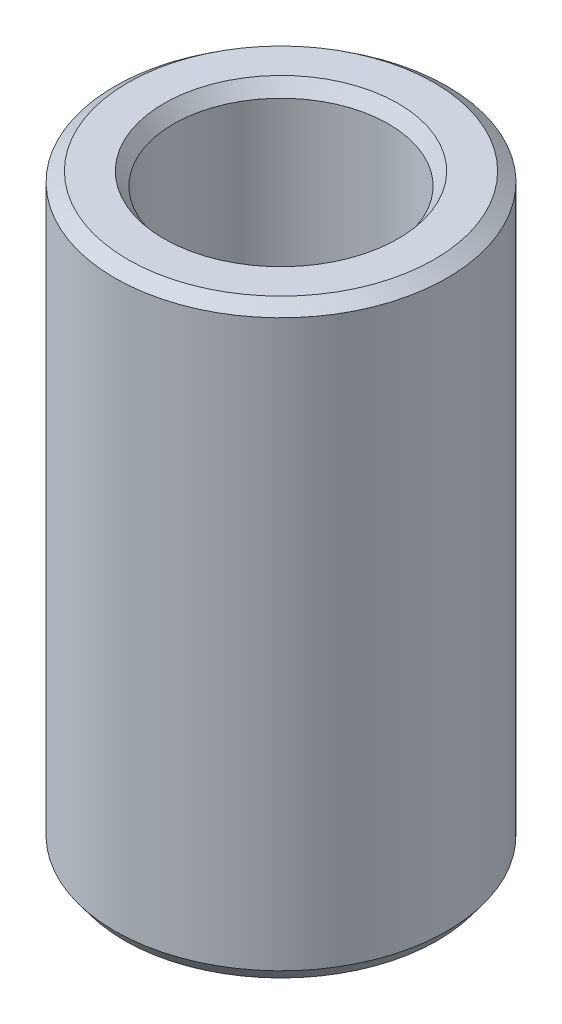
SolidWorks part; units mm, degrees
ref_plane "Front Plane" through (0, 0, 0) normal (0, 0, 1) x (1, 0, 0)
ref_plane "Top Plane" through (0, 0, 0) normal (0, 1, 0) x (1, 0, 0)
ref_plane "Right Plane" through (0, 0, 0) normal (1, 0, 0) x (0, 0, -1)
sketch "Sketch1" plane through (0, 0, 0) normal (0, 1, 0) x (1, 0, 0)
  circle A0 centre (0, 0) radius 37.5
  dimension "SLEEVE_OD" = 75
extrude "Boss-Extrude1" add sketch "Sketch1" along normal blind 132.7355
sketch "Sketch2" plane through (0, 0, 0) normal (0, 1, 0) x (1, 0, 0)
  circle A0 centre (0, 0) radius 24.2804
  dimension "BORE_D" = 48.5607
extrude "Cut-Extrude1" cut sketch "Sketch2" along normal through all
chamfer "Chamfer1" distance 2.164 angle 53.51 4 edges at (0, 132.7355, 24.2804) (0, 0, 24.2804) (0, 0, 37.5) (0, 132.7355, 37.5) first distance on face at (0, 132.7355, 24.2804) first distance on face at (0, 0, 24.2804) first distance on face at (0, 132.7355, 37.5)
